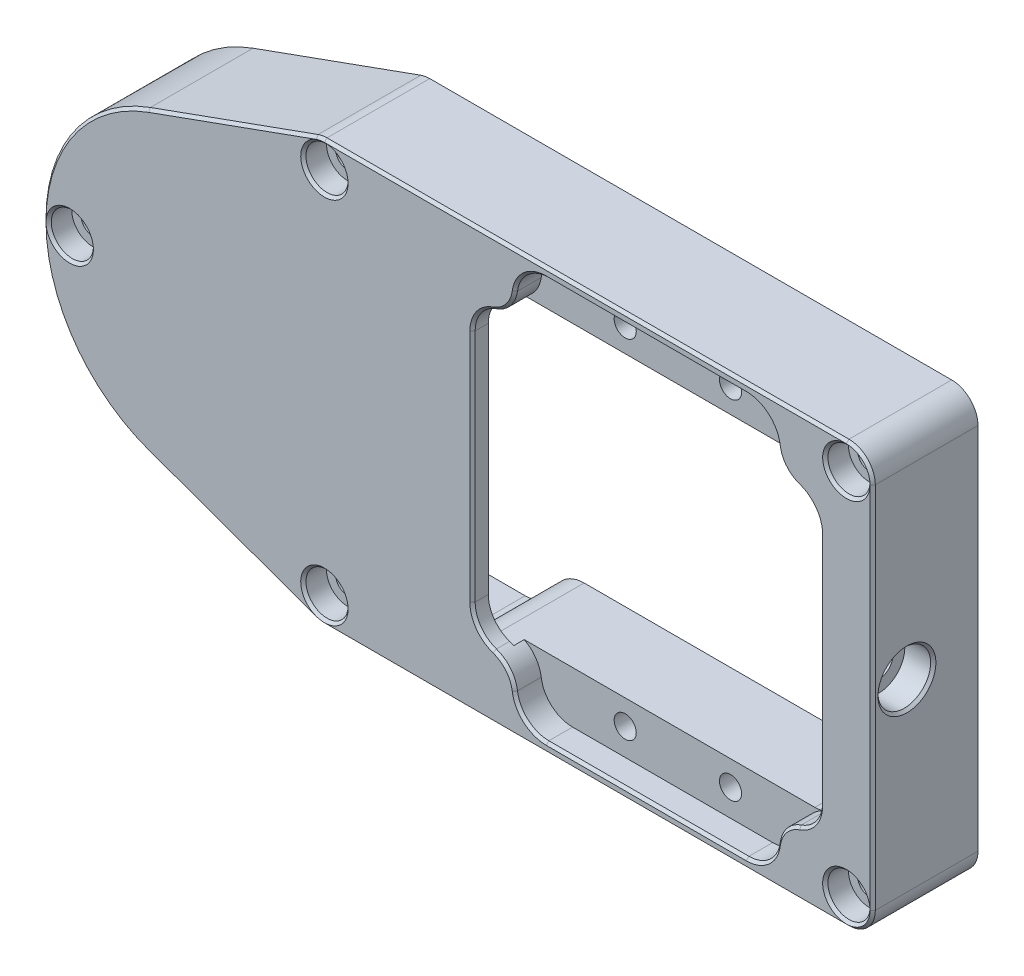
SolidWorks part; units mm, degrees
material "Alumina"
ref_plane "Plan de face" through (0, 0, 0) normal (0, 0, 1) x (1, 0, 0)
ref_plane "Plan de dessus" through (0, 0, 0) normal (0, 1, 0) x (1, 0, 0)
ref_plane "Plan de droite" through (0, 0, 0) normal (1, 0, 0) x (0, 0, -1)
sketch "Sketch2" plane through (0, 0, 0) normal (0, 0, 1) x (1, 0, 0)
  line L8 (-30, 40) -> (75, 40)
  line L9 (75, 40) -> (75, -40)
  line L11 (-30, 40) -> (-62.6732, 28.2224)
  line L12 (-62.6732, -28.2224) -> (-30, -40)
  line L19 (-30, -40) -> (75, -40)
  arc A6 (-62.6732, 28.2224) -> (-62.6732, -28.2224) centre (-52.5, 0) ccw
  point P5 (75, 0)
  dimension "D6" = 30
  dimension "D7" = 80
  dimension "D1" = 127.5
  dimension "D2" = 30
  dimension "D3" = 105
extrude "Boss-Extrude1" add sketch "Sketch2" along normal blind 20
fillet "Fillet1" radius 5 4 edges at (-30, 40, 10) (75, 40, 10) (75, -40, 10) (-30, -40, 10)
hole_wizard "CBORE for M4 Hex Socket Head Cap Screw1" positions "3DSketch3" profile "Sketch7" counterbore size "M4" standard "ISO" end condition through all
sketch3d "3DSketch3"
  line L11 (83.666, -0.0498, 20) -> (-85, -0.0498, 20) construction
  line L12 (7.5, 40, 20) -> (7.5, -40, 20) construction
  line L13 (70, 40, 20) -> (-29.1263, 40, 20) construction
  line L14 (-29.1263, -40, 20) -> (70, -40, 20) construction
  arc A0 (-29.1263, 40, 20) -> (-30.8219, 39.7037, 20) centre (-29.1263, 35, 20) ccw construction
  arc A1 (-30.8219, -39.7037, 20) -> (-29.1263, -40, 20) centre (-29.1263, -35, 20) ccw construction
  arc A2 (70, -40, 20) -> (75, -35, 20) centre (70, -35, 20) ccw construction
  arc A3 (75, 35, 20) -> (70, 40, 20) centre (70, 35, 20) ccw construction
  arc A4 (-62.6732, 28.2224, 20) -> (-62.6732, -28.2224, 20) centre (-52.5, 0, 20) ccw construction
  point P0 (-29.1263, 35, 20)
  point P4 (-29.1263, -35, 20)
  point P8 (70, 35, 20)
  point P12 (70, -35, 20)
  point P65 (-77.5, -0.0498, 20)
  point P87 (-29.1263, 35, 25)
  point P92 (-29.1263, -35, 25)
  point P97 (70, -35, 25)
  point P102 (70, 35, 25)
  point P117 (-52.5, 0, 50)
  dimension "D1" = 60
  dimension "D2" = 85
sketch "Sketch7" plane through (-29.1263, 35, 20) normal (1, 0, 0) x (0, -1, 0)
  line L0 (0, 0) -> (0, 20)
  line L1 (0, 20) -> (2.25, 20)
  line L3 (2.25, 20) -> (2.25, 4.4)
  line L4 (2.25, 4.4) -> (4, 4.4)
  line L5 (4, 4.4) -> (4, 0)
  line L7 (4, 0) -> (0, 0)
  line L11 (0, -6.35) -> (0, 107.95) construction
  dimension "Thru Hole Dia." = 4.5
  dimension "Thru Hole Depth" = 20
  dimension "C'Bore Dia." = 8
  dimension "C'Bore Depth" = 4.4
sketch "Sketch10" plane through (0, 0, 20) normal (0, 0, 1) x (1, 0, 0)
  line L1 (7, -28.3) -> (65, -28.3)
  line L3 (7, 28.3) -> (65, 28.3)
  line L4 (65, -28.3) -> (65, 28.3)
  line L5 (7, -28.3) -> (65, 28.3) construction
  line L6 (7, 28.3) -> (65, -28.3) construction
  line L7 (7, 28.3) -> (-1, 28.3)
  line L9 (7, -28.3) -> (-1, -28.3)
  line L10 (-1, 28.3) -> (-1, -28.3)
  line L11 (57, -38.1) -> (15, -38.1)
  line L12 (57, -38.1) -> (57, 38.1)
  line L13 (57, 38.1) -> (15, 38.1)
  line L15 (57, -38.1) -> (15, 38.1) construction
  line L16 (57, 38.1) -> (15, -38.1) construction
  line L17 (15, 38.1) -> (7, 38.1)
  line L19 (15, -38.1) -> (7, -38.1)
  line L20 (7, 38.1) -> (7, -38.1)
  point P0 (36, 0)
  point P10 (36, 0)
  point P18 (7, 0)
  dimension "D1" = 36
  dimension "D2" = 58
  dimension "D3" = 56.6
  dimension "D4" = 8
  dimension "D5" = 76.2
  dimension "D6" = 42
  dimension "D7" = 8
extrude "Cut-Extrude3" cut sketch "Sketch10" against normal blind 5 contours L3 L20 L1 L12 | L17 L20 L3 L12 L13 | L20 L3 L7 L10 L9 L1 | L1 L20 L19 L11 L12 | L12 L1 L4 L3 region at (32, 0, 20) region at (3, 0, 20) region at (32, -33.2, 20) region at (61, 0, 20) region at (32, 33.2, 20)
extrude "Cut-Extrude4" cut sketch "Sketch10<4>" against normal through all contours L3 L20 L1 L12 | L20 L3 L7 L10 L9 L1 | L12 L1 L4 L3 region at (32, 0, 20) region at (3, 0, 20) region at (61, 0, 20)
sketch "Sketch10<4>" plane through (0, 0, 20) normal (0, 0, 1) x (1, 0, 0) same geometry as "Sketch10"
fillet "Fillet4" radius 6 8 edges at (65, 28.3, 10) (65, -28.3, 10) (57, -38.1, 17.5) (7, -38.1, 17.5) (-1, -28.3, 10) (-1, 28.3, 10) (57, 38.1, 17.5) (7, 38.1, 17.5)
fillet "Fillet5" radius 6 4 edges at (7, 28.3, 17.5) (57, 28.3, 17.5) (57, -28.3, 17.5) (7, -28.3, 17.5)
sketch "Sketch8" plane through (0, 0, 0) normal (0, 0, -1) x (-1, 0, 0)
  line L2 (-65, -22.3) -> (-65, 22.3) construction
  line L3 (-59, 28.3) -> (5, 28.3)
  line L4 (-65, -22.3) -> (-65, 22.3)
  line L5 (-59, -28.3) -> (5, -28.3)
  line L7 (5, 28.3) -> (5, 36)
  line L9 (5, -28.3) -> (5, -36)
  line L10 (61.3168, 24.4594) -> (29.4655, 35.9407)
  line L11 (29.1263, 36) -> (-70, 36)
  line L12 (-71, 35) -> (-71, -35)
  line L13 (-70, -36) -> (29.1263, -36)
  line L14 (29.4655, -35.9407) -> (61.3168, -24.4594)
  line L15 (61.3168, 24.4594) -> (35.2694, 33.8486)
  line L16 (22.9569, 36) -> (5, 36)
  line L18 (5, -36) -> (22.9569, -36)
  line L19 (35.2694, -33.8486) -> (61.3168, -24.4594)
  arc A0 (-65, -22.3) -> (-59, -28.3) centre (-59, -22.3) ccw construction
  arc A1 (-59, 28.3) -> (-65, 22.3) centre (-59, 22.3) ccw construction
  arc A2 (-65, -22.3) -> (-59, -28.3) centre (-59, -22.3) ccw
  arc A3 (-59, 28.3) -> (-65, 22.3) centre (-59, 22.3) ccw
  arc A10 (29.4655, 35.9407) -> (29.1263, 36) centre (29.1263, 35) ccw
  arc A11 (-70, 36) -> (-71, 35) centre (-70, 35) ccw
  arc A12 (-71, -35) -> (-70, -36) centre (-70, -35) ccw
  arc A13 (29.1263, -36) -> (29.4655, -35.9407) centre (29.1263, -35) ccw
  arc A14 (61.3168, -24.4594) -> (61.3168, 24.4594) centre (52.5, 0) ccw
  arc A19 (61.3168, -24.4594) -> (77.7263, -6.2957) centre (52.5, 0) ccw
  circle A23 centre (29.1263, 35) radius 6.25
  arc A24 (22.9569, 36) -> (35.2694, 33.8486) centre (29.1263, 35) ccw
  circle A26 centre (29.1263, -35) radius 6.25
  arc A27 (35.2694, -33.8486) -> (22.9569, -36) centre (29.1263, -35) ccw
  arc A28 (77.7511, 6.1952) -> (61.3168, 24.4594) centre (52.5, 0) ccw
  circle A29 centre (77.5, -0.0498) radius 6.25
  arc A30 (77.7511, 6.1952) -> (77.7263, -6.2957) centre (77.5, -0.0498) ccw
  dimension "D7" = 5
  dimension "D1" = 4
  dimension "D4" = 4
  dimension "D5" = 4
  dimension "D6" = 4
extrude "Cut-Extrude1" cut sketch "Sketch8" against normal offset from surface (17 mm away) 3 up to face at (-25.1263, 35, 20)
fillet "Fillet2" radius 6 8 edges at (-77.7263, -6.2957, 8.5) (-77.7511, 6.1952, 8.5) (-35.2694, 33.8486, 8.5) (-22.9569, 36, 8.5) (-35.2694, -33.8486, 8.5) (-22.9569, -36, 8.5) (-5, -36, 8.5) (-5, 36, 8.5)
fillet "Fillet6" radius 6 2 edges at (-5, -28.3, 8.5) (-5, 28.3, 8.5)
hole_wizard "Tap Drill for M5 Tap1" positions "Sketch13" profile "Sketch14" hole size "M5" standard "ISO"
sketch "Sketch13" plane through (0, 0, 15) normal (0, 0, 1) x (1, 0, 0)
  line L0 (33, 36.3) -> (33, -36.3) construction
  line L5 (23, -33) -> (43, -33) construction
  line L6 (23, -33) -> (23, 33) construction
  line L7 (23, 33) -> (43, 33) construction
  line L8 (43, -33) -> (43, 33) construction
  line L9 (23, -33) -> (43, 33) construction
  line L10 (23, 33) -> (43, -33) construction
  line L11 (65, -22.3) -> (65, 22.3) construction
  point P8 (33, 0)
  point P9 (43, 33)
  point P12 (23, -33)
  point P13 (23, 33)
  point P14 (43, -33)
  dimension "D1" = 20
  dimension "D2" = 66
  dimension "D3" = 32
sketch "Sketch14" plane through (43, -33, 15) normal (1, 0, 0) x (0, -1, 0)
  line L0 (0, 0) -> (0, 11.2618)
  line L1 (0, 11.2618) -> (2.1, 10)
  line L2 (2.1, 10) -> (2.1, 0)
  line L5 (2.1, 0) -> (0, 0)
  line L10 (0, 11.2618) -> (-2.1, 10) construction
  line L11 (0, -6.35) -> (0, 107.95) construction
  dimension "Hole Dia." = 4.2
  dimension "Hole Depth" = 10
  dimension "Drill Angle" = 118
hole_wizard "CBORE for M5 Hex Socket Head Cap Screw2" positions "Sketch17" profile "Sketch19" counterbore size "M5" standard "ISO"
sketch "Sketch17" plane through (75, 0, 0) normal (1, 0, 0) x (0, 0, -1)
  line L4 (-20, -35) -> (-20, 35) construction
  point P21 (-13.5, 0)
  dimension "D1" = 6.5
sketch "Sketch19" plane through (75, 0, 13.5) normal (0, 1, 0) x (0, 0, -1)
  line L0 (0, 0) -> (0, 21.6524)
  line L1 (0, 21.6524) -> (2.75, 20)
  line L2 (2.75, 20) -> (2.75, 5.4)
  line L3 (2.75, 5.4) -> (5, 5.4)
  line L4 (5, 5.4) -> (5, 0)
  line L5 (5, 0) -> (0, 0)
  line L10 (0, 21.6524) -> (-2.75, 20) construction
  line L11 (0, -6.35) -> (0, 107.95) construction
  dimension "Hole Dia." = 5.5
  dimension "Hole Depth" = 20
  dimension "C'Bore Dia." = 10
  dimension "C'Bore Depth" = 5.4
  dimension "Drill Angle" = 118
chamfer "Chamfer1" distance 0.5 angle 45 32 edges at (-73.5, -0.0498, 20) (-25.1263, -35, 20) (74, -35, 20) (74, 35, 20) (-25.1263, 35, 20) (-1, 0, 20) (0.1164, -25.7858, 20) (0.1164, 25.7858, 20) (5.7483, -29.8544, 20) (5.7483, 29.8544, 20) (9.0406, -36.6081, 20) (9.0406, 36.6081, 20) (32, -38.1, 20) (32, 38.1, 20) (54.9594, -36.6081, 20) (54.9594, 36.6081, 20) (58.2517, -29.8544, 20) (58.2517, 29.8544, 20) (63.8836, -25.7858, 20) (63.8836, 25.7858, 20) (65, 0, 20) (-29.987, 39.9254, 20) (-46.7475, 33.9631, 20) (20.4368, 40, 20) (-82.5, 0, 20) (73.5355, 38.5355, 20) (-46.7475, -33.9631, 20) (75, 0, 20) (-29.987, -39.9254, 20) (73.5355, -38.5355, 20) (20.4368, -40, 20) (75, 0, 8.5)
